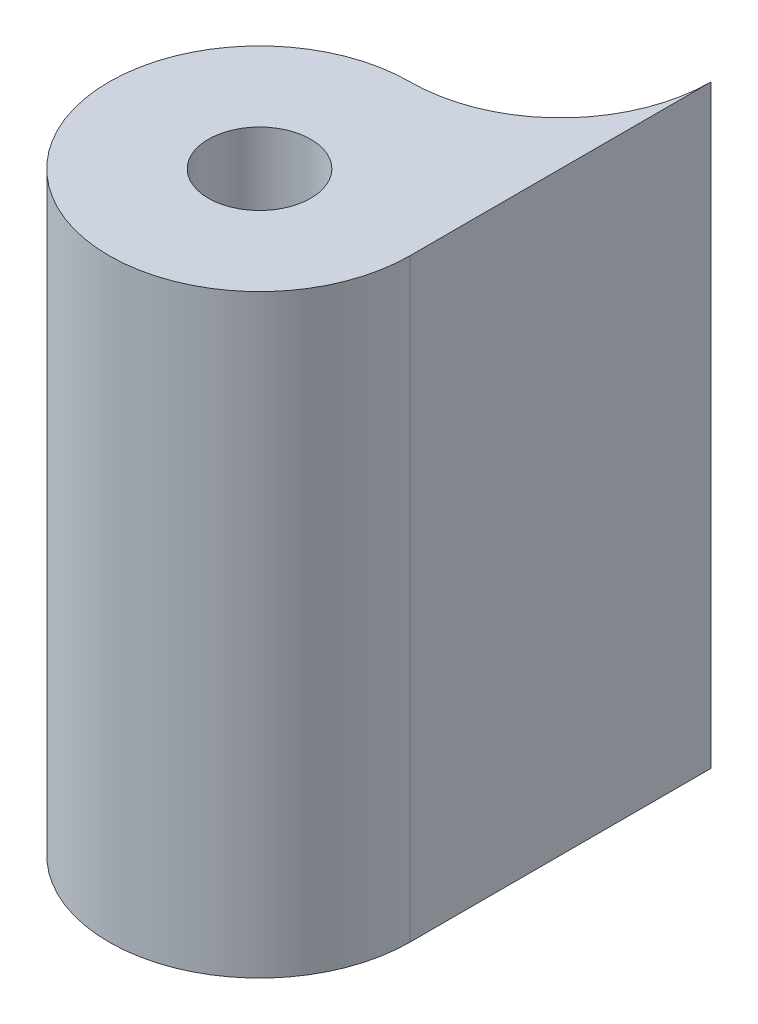
SolidWorks part; units mm, degrees
ref_plane "Front Plane" through (0, 0, 0) normal (0, 0, 1) x (1, 0, 0)
ref_plane "Top Plane" through (0, 0, 0) normal (0, 1, 0) x (1, 0, 0)
ref_plane "Right Plane" through (0, 0, 0) normal (1, 0, 0) x (0, 0, -1)
sketch "Sketch1" plane through (0, 0, 0) normal (0, 0, 1) x (1, 0, 0)
  line L3 (55, -90) -> (-55, -90)
  line L4 (75, -70) -> (75, 70)
  line L5 (55, 90) -> (-55, 90)
  line L6 (-75, -70) -> (-75, 70)
  line L7 (75, -90) -> (-75, 90) construction
  line L8 (75, 90) -> (-75, -90) construction
  arc A2 (-55, -90) -> (-75, -70) centre (-55, -70) cw
  arc A3 (55, -90) -> (75, -70) centre (55, -70) ccw
  arc A4 (75, 70) -> (55, 90) centre (55, 70) ccw
  arc A5 (-55, 90) -> (-75, 70) centre (-55, 70) ccw
  point P0 (0, 0)
  dimension "D3" = 20
  dimension "D1" = 180
  dimension "D2" = 150
extrude "Boss-Extrude1" add sketch "Sketch1" along normal blind 20
shell "Shell1" thickness 10 removed face at (0, 0, 20)
sketch "Sketch8" plane through (0, 0, 4) normal (0, 0, 1) x (1, 0, 0)
  line L0 (75.1597, 25) -> (-92.0515, 25) construction
  dimension "D1" = 25
sketch "Sketch2" plane through (0, 0, 20) normal (0, 0, 1) x (1, 0, 0)
  line L10 (-72, 70) -> (-72, -70)
  line L11 (-55, -87) -> (55, -87)
  line L12 (72, -70) -> (72, 70)
  line L13 (55, 87) -> (-55, 87)
  line L14 (-70, 70) -> (-70, -70)
  line L15 (-55, -85) -> (55, -85)
  line L16 (70, -70) -> (70, 70)
  line L17 (55, 85) -> (-55, 85)
  line L18 (-70, 70) -> (-70, -70) construction
  line L19 (-55, -85) -> (55, -85) construction
  line L20 (70, -70) -> (70, 70) construction
  line L21 (55, 85) -> (-55, 85) construction
  line L22 (-68, 70) -> (-68, -70)
  line L23 (-55, -83) -> (55, -83)
  line L24 (68, -70) -> (68, 70)
  line L25 (55, 83) -> (-55, 83)
  arc A8 (-72, -70) -> (-55, -87) centre (-55, -70) ccw
  arc A9 (55, -87) -> (72, -70) centre (55, -70) ccw
  arc A10 (72, 70) -> (55, 87) centre (55, 70) ccw
  arc A11 (-55, 87) -> (-72, 70) centre (-55, 70) ccw
  arc A12 (-55, 85) -> (-70, 70) centre (-55, 70) ccw
  arc A13 (-70, -70) -> (-55, -85) centre (-55, -70) ccw
  arc A14 (55, -85) -> (70, -70) centre (55, -70) ccw
  arc A15 (70, 70) -> (55, 85) centre (55, 70) ccw
  arc A16 (-55, 85) -> (-70, 70) centre (-55, 70) ccw construction
  arc A17 (-70, -70) -> (-55, -85) centre (-55, -70) ccw construction
  arc A18 (55, -85) -> (70, -70) centre (55, -70) ccw construction
  arc A19 (70, 70) -> (55, 85) centre (55, 70) ccw construction
  arc A20 (-68, -70) -> (-55, -83) centre (-55, -70) ccw
  arc A21 (55, -83) -> (68, -70) centre (55, -70) ccw
  arc A22 (68, 70) -> (55, 83) centre (55, 70) ccw
  arc A23 (-55, 83) -> (-68, 70) centre (-55, 70) ccw
  dimension "D1" = 5
  dimension "D2" = 2
  dimension "D3" = 2
extrude "Cut-Extrude1" [suppressed] cut sketch "Sketch2" against normal blind 3
sketch "Sketch3" plane through (0, 0, 0) normal (0, 0, 1) x (1, 0, 0)
  line L0 (-55, -80) -> (55, -80) construction
  circle A0 centre (0, -36.75) radius 32.5
  dimension "D2" = 65
  dimension "D1" = 43.25
extrude "Cut-Extrude5" cut sketch "Sketch3" along normal through all
sketch "Sketch4" plane through (0, 0, 0) normal (0, 0, 1) x (1, 0, 0)
  line L0 (75.1597, 25) -> (-92.0515, 25) construction
  line L1 (-30.75, 13.25) -> (-9.25, 13.25)
  line L2 (-31.75, 14.25) -> (-31.75, 35.75)
  line L3 (-30.75, 36.75) -> (-9.25, 36.75)
  line L4 (-8.25, 14.25) -> (-8.25, 35.75)
  line L5 (-31.75, 13.25) -> (-8.25, 36.75) construction
  line L6 (-31.75, 36.75) -> (-8.25, 13.25) construction
  arc A0 (-8.25, 14.25) -> (-9.25, 13.25) centre (-9.25, 14.25) cw
  arc A1 (-31.75, 35.75) -> (-30.75, 36.75) centre (-30.75, 35.75) cw
  arc A2 (-30.75, 13.25) -> (-31.75, 14.25) centre (-30.75, 14.25) cw
  arc A3 (-9.25, 36.75) -> (-8.25, 35.75) centre (-9.25, 35.75) cw
  point P0 (-20, 25)
  dimension "D3" = 1
  dimension "D1" = 23.5
  dimension "D2" = 20
extrude "Cut-Extrude6" cut sketch "Sketch4" along normal through all
sketch "Sketch5" plane through (0, 0, 0) normal (0, 0, 1) x (1, 0, 0)
  line L0 (75.1597, 25) -> (-92.0515, 25) construction
  circle A0 centre (20, 25) radius 17.5
  dimension "D1" = 35
  dimension "D2" = 20
extrude "Cut-Extrude7" cut sketch "Sketch5" along normal through all
sketch "Sketch6" plane through (0, 0, 0) normal (0, 1, 0) x (1, 0, 0)
  line L0 (75, -20) -> (75, 0) construction
  line L1 (75, -20) -> (75, -10)
  line L2 (55, -20) -> (-55, -20) construction
  arc A0 (75, -20) -> (80, -15) centre (80, -20) ccw
  circle A1 centre (80, -20) radius 1.7
  arc A2 (80, -15) -> (75, -10) centre (80, -10) cw
  dimension "D1" = 3.4
  dimension "D2" = 10
extrude "Boss-Extrude2" add sketch "Sketch6" along normal mid plane 100
extrude "Cut-Extrude8" cut sketch "Sketch6<2>" against normal mid plane 70
sketch "Sketch6<2>" plane through (0, 0, 0) normal (0, 1, 0) x (1, 0, 0) same geometry as "Sketch6"
sketch "Sketch9" plane through (0, 0, 0) normal (0, 1, 0) x (1, 0, 0)
  line L0 (55, -20) -> (-55, -20) construction
  line L1 (-75, -20) -> (-75, 0) construction
  line L2 (-75, -10) -> (-75, -20)
  circle A0 centre (-80, -20) radius 1.7
  arc A1 (-80, -15) -> (-75, -20) centre (-80, -20) ccw
  arc A2 (-80, -15) -> (-75, -10) centre (-80, -10) ccw
  dimension "D1" = 10
  dimension "D2" = 3.4
extrude "Boss-Extrude3" add sketch "Sketch9" along normal mid plane 65
extrude "Cut-Extrude10" cut sketch "Sketch9<2>" against normal mid plane 25.5
sketch "Sketch9<2>" plane through (0, 0, 0) normal (0, 1, 0) x (1, 0, 0) same geometry as "Sketch9"
sketch "Sketch7" plane through (0, 0, 4) normal (0, 0, 1) x (1, 0, 0)
  line L1 (-26, -0.75) -> (26, -0.75)
  line L2 (-36, -10.75) -> (-36, -62.75)
  line L3 (-26, -72.75) -> (26, -72.75)
  line L4 (36, -10.75) -> (36, -62.75)
  line L5 (-36, -0.75) -> (36, -72.75) construction
  line L6 (-36, -72.75) -> (36, -0.75) construction
  line L7 (8, 47) -> (32, 47)
  line L8 (-2, 37) -> (-2, 13)
  line L9 (8, 3) -> (32, 3)
  line L10 (42, 37) -> (42, 13)
  line L11 (-2, 47) -> (42, 3) construction
  line L12 (-2, 3) -> (42, 47) construction
  circle A0 centre (20, 25) radius 17.5 construction
  arc A1 (-36, -62.75) -> (-26, -72.75) centre (-26, -62.75) ccw
  arc A2 (26, -72.75) -> (36, -62.75) centre (26, -62.75) ccw
  arc A3 (26, -0.75) -> (36, -10.75) centre (26, -10.75) cw
  arc A4 (-26, -0.75) -> (-36, -10.75) centre (-26, -10.75) ccw
  arc A5 (-2, 13) -> (8, 3) centre (8, 13) ccw
  arc A6 (32, 3) -> (42, 13) centre (32, 13) ccw
  arc A7 (32, 47) -> (42, 37) centre (32, 37) cw
  arc A8 (8, 47) -> (-2, 37) centre (8, 37) ccw
  point P0 (0, -36.75)
  point P5 (20, 25)
  dimension "D1" = 22
  dimension "D5" = 10
  dimension "D2" = 22
  dimension "D3" = 36
  dimension "D4" = 36
extrude "Cut-Extrude9" cut sketch "Sketch7" against normal blind 2
fillet "Fillet1" radius 5 16 edges at (75, 0, 0) (69.1421, -84.1421, 0) (0, -90, 0) (-69.1421, -84.1421, 0) (-75, 0, 0) (-69.1421, 84.1421, 0) (0, 90, 0) (69.1421, 84.1421, 0) (0, 80, 4) (62.0711, 77.0711, 4) (65, 0, 4) (62.0711, -77.0711, 4) (0, -80, 4) (-62.0711, -77.0711, 4) (-65, 0, 4) (-62.0711, 77.0711, 4)
fillet "Fillet2" radius 0.5 46 edges at (-8.5429, 13.5429, 0) (-20, 13.25, 0) (-31.4571, 13.5429, 0) (-31.75, 25, 0) (-31.4571, 36.4571, 0) (-20, 36.75, 0) (-8.5429, 36.4571, 0) (75, 60, 20) (69.1421, 84.1421, 20) (0, 90, 20) (-69.1421, 84.1421, 20) (75, -60, 20) (69.1421, -84.1421, 20) (0, -90, 20) (-69.1421, -84.1421, 20) (-62.0711, 77.0711, 20) (0, 80, 20) (62.0711, 77.0711, 20) (65, 0, 20) (62.0711, -77.0711, 20) (0, -80, 20) (-62.0711, -77.0711, 20) (-8.25, 25, 0) (37.5, 25, 0) (75, 0, 20) (-75, 51.25, 20) (-75, -51.25, 20) (-75, 0, 20) (-65, 0, 20) (32.5, -36.75, 0) (0.9289, 44.0711, 4) (20, 47, 4) (39.0711, 44.0711, 4) (42, 25, 4) (39.0711, 5.9289, 4) (20, 3, 4) (0.9289, 5.9289, 4) (33.0711, -3.6789, 4) (36, -36.75, 4) (33.0711, -69.8211, 4) (0, -72.75, 4) (-33.0711, -69.8211, 4) (-36, -36.75, 4) (-33.0711, -3.6789, 4) (-2, 25, 4) (0, -0.75, 4)
sketch "Sketch10" plane through (-75, 0, 0) normal (-1, 0, 0) x (0, 0, 1)
  line L1 (-13.4851, 94.3477) -> (32.6567, 94.3477)
  line L2 (-13.4851, 94.3477) -> (-13.4851, -94.1049)
  line L3 (-13.4851, -94.1049) -> (32.6567, -94.1049)
  line L4 (32.6567, 94.3477) -> (32.6567, -94.1049)
extrude "Cut-Extrude11" cut sketch "Sketch10" against normal through all
